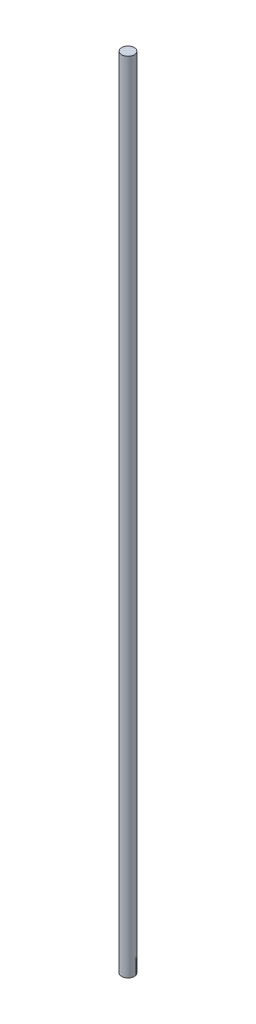
SolidWorks part; units mm, degrees
ref_plane "Ebene vorne" through (0, 0, 0) normal (0, 0, 1) x (1, 0, 0)
ref_plane "Ebene oben" through (0, 0, 0) normal (0, 1, 0) x (1, 0, 0)
ref_plane "Ebene rechts" through (0, 0, 0) normal (1, 0, 0) x (0, 0, -1)
sketch "Position" plane through (0, 0, 0) normal (0, 1, 0) x (1, 0, 0)
  circle A0 centre (14, 0) radius 1.5
  circle A1 centre (0, 0) radius 4.5
sketch "Length" plane through (0, 0, 0) normal (0, 0, 1) x (1, 0, 0)
  line L0 (0, 218) -> (0, 618)
  line L4 (14, 237) -> (14, 618)
  point P7 (0, 210.9748)
  point P9 (0, 217.541)
sketch "Skizze3" plane through (0, 0, 0) normal (0, 1, 0) x (1, 0, 0)
  circle A0 centre (14, 0) radius 3
extrude "Aufsatz-Linear austragen1" add sketch "Skizze3" along normal up to vertex (618 mm away) from vertex up to point (14, 618, 0) starting at point (14, 237, 0)
sketch "Skizze4" plane through (0, 0, 0) normal (0, 1, 0) x (1, 0, 0)
  circle A0 centre (14, 0) radius 1.25
extrude "Schnitt-Linear austragen1" cut sketch "Skizze4" along normal blind 20 from vertex starting at point (14, 237, 0)
